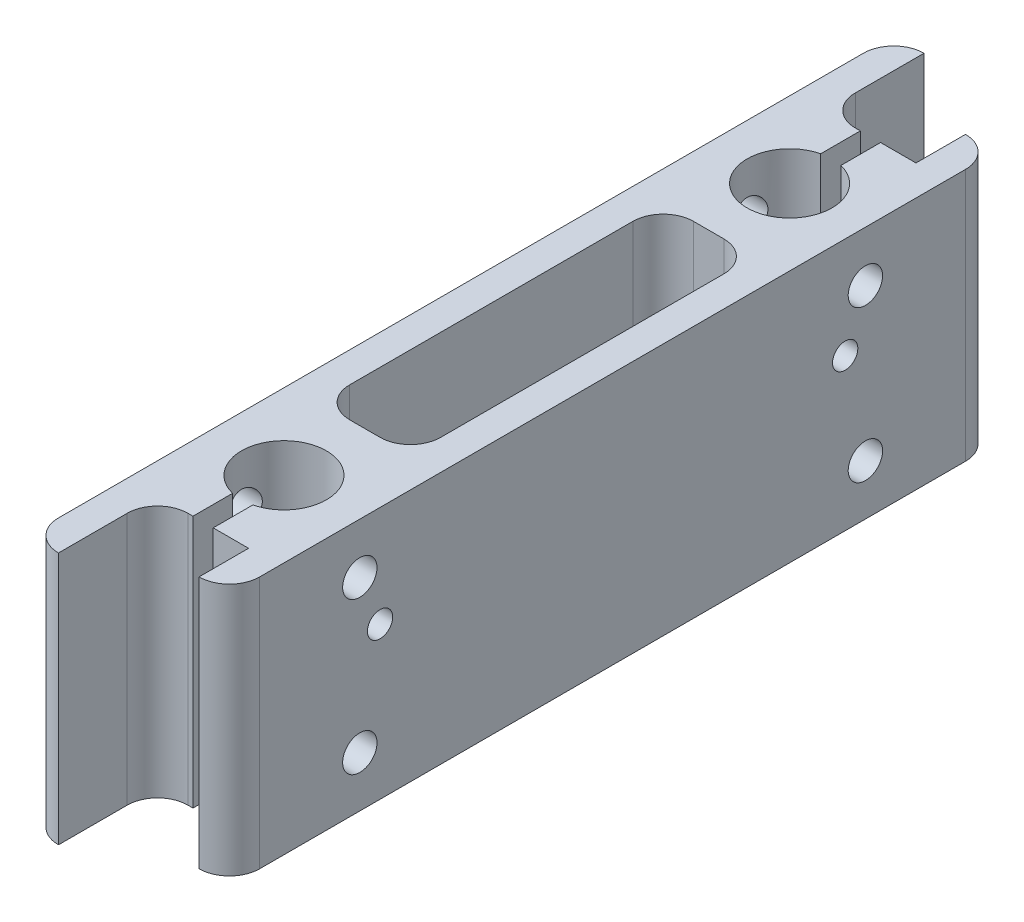
SolidWorks part; units mm, degrees
material "POM 乙缩醛共聚物"
ref_plane "前视基准面" through (0, 0, 0) normal (0, 0, 1) x (1, 0, 0)
ref_plane "上视基准面" through (0, 0, 0) normal (0, 1, 0) x (1, 0, 0)
ref_plane "右视基准面" through (0, 0, 0) normal (1, 0, 0) x (0, 0, -1)
sketch "草图2" plane through (0, 0, 0) normal (0, 1, 0) x (1, 0, 0)
  line L0 (-10.5, 44.6) -> (-10.5, 34.8)
  line L5 (-14.6, 25.2) -> (12.8735, -22.22) construction
  line L6 (4.2, -25.2) -> (-4.2, 25.2) construction
  line L7 (-13.5, 44.6) -> (-10.5, 44.6)
  line L8 (-13.5, 44.6) -> (-13.5, -41)
  line L9 (-13.5, -41) -> (-10.5, -41)
  line L10 (1.5, 39.7) -> (1.5, -36.1)
  line L11 (-13.5, 44.6) -> (10.9271, -36.1) construction
  line L12 (-13.5, -41) -> (13.072, 39.7) construction
  line L13 (-10.5, 34.8) -> (-1.5, 34.8)
  line L14 (-1.5, 34.8) -> (-1.5, 39.7)
  line L15 (-10.5, -41) -> (-10.5, -31.2)
  line L16 (-10.5, -31.2) -> (-1.5, -31.2)
  line L17 (-1.5, -31.2) -> (-1.5, -36.1)
  line L18 (-1.5, 39.7) -> (1.5, 39.7)
  line L19 (-1.5, -36.1) -> (1.5, -36.1)
  circle A0 centre (-6, -23.2) radius 4.2
  circle A1 centre (-6, 26.8) radius 4.2
  point P0 (0, 0)
  point P6 (0, 0)
  dimension "D14" = 8.4
  dimension "D15" = 8.4
  dimension "D4" = 7.5
  dimension "D16" = 8
  dimension "D18" = 8
  dimension "D2" = 50
  dimension "D8" = 7.5
  dimension "D1" = 10.4
  dimension "D3" = 85.6
  dimension "D5" = 9
  dimension "D6" = 3
  dimension "D7" = 3
  dimension "D9" = 3
  dimension "D10" = 4.9
  dimension "D11" = 9.8
  dimension "D12" = 4.9
  dimension "D13" = 9.8
extrude "凸台-拉伸1" add sketch "草图2" along normal blind 25
fillet "圆角1" radius 3 6 edges at (1.5, 12.5, 36.1) (1.5, 12.5, -39.7) (-10.5, 12.5, -34.8) (-10.5, 12.5, 31.2) (-13.5, 12.5, -44.6) (-13.5, 12.5, 41)
sketch "草图3" plane through (0, 25, 0) normal (0, 1, 0) x (1, 0, 0)
  line L5 (-13.5, 41.6) -> (-13.5, -38) construction
  line L6 (-7.5, 18.8) -> (-4.5, 18.8)
  line L7 (-10.5, 15.8) -> (-10.5, -12.2)
  line L8 (-7.5, -15.2) -> (-4.5, -15.2)
  line L9 (-1.5, 15.8) -> (-1.5, -12.2)
  line L10 (-10.5, 18.8) -> (-1.5, -15.2) construction
  line L11 (-10.5, -15.2) -> (-1.5, 18.8) construction
  line L12 (1.5, -33.1) -> (1.5, 36.7) construction
  circle A5 centre (-6, 26.8) radius 4.2 construction
  circle A6 centre (-6, -23.2) radius 4.2 construction
  arc A7 (-10.5, -12.2) -> (-7.5, -15.2) centre (-7.5, -12.2) ccw
  arc A8 (-4.5, -15.2) -> (-1.5, -12.2) centre (-4.5, -12.2) ccw
  arc A9 (-4.5, 18.8) -> (-1.5, 15.8) centre (-4.5, 15.8) cw
  arc A10 (-7.5, 18.8) -> (-10.5, 15.8) centre (-7.5, 15.8) ccw
  point P4 (-6, 1.8)
  dimension "D3" = 8
  dimension "D5" = 3
  dimension "D1" = 3
  dimension "D2" = 3
  dimension "D4" = 8
extrude "切除-拉伸1" cut sketch "草图3" against normal blind 25
sketch "草图4" plane through (0, 25, 0) normal (0, 1, 0) x (1, 0, 0)
  line L1 (-5, -36.7224) -> (-7, -36.7224)
  line L2 (-5, -36.7224) -> (-5, -26.95)
  line L3 (-5, -26.95) -> (-7, -26.95)
  line L4 (-7, -36.7224) -> (-7, -26.95)
  line L5 (-5, -36.7224) -> (-7, -26.95) construction
  line L6 (-5, -26.95) -> (-7, -36.7224) construction
  line L7 (-5, 37.1632) -> (-7, 37.1632)
  line L8 (-5, 37.1632) -> (-5, 27.1332)
  line L9 (-5, 27.1332) -> (-7, 27.1332)
  line L10 (-7, 37.1632) -> (-7, 27.1332)
  line L11 (-5, 37.1632) -> (-7, 27.1332) construction
  line L12 (-5, 27.1332) -> (-7, 37.1632) construction
  circle A0 centre (-6, 26.8) radius 4.2 construction
  circle A1 centre (-6, -23.2) radius 4.2 construction
  point P4 (-6, -31.8362)
  point P9 (-6, 32.1482)
  dimension "D1" = 2
  dimension "D2" = 1
  dimension "D3" = 2
  dimension "D4" = 1
extrude "切除-拉伸2" cut sketch "草图4" against normal blind 25
sketch "草图5" plane through (1.5, 0, 0) normal (1, 0, 0) x (0, 0, -1)
  line L0 (-33.1, 25) -> (36.7, 25) construction
  line L2 (-31.2, 25) -> (-31.2, 0) construction
  line L3 (34.8, 25) -> (34.8, 0) construction
  circle A0 centre (-21.2, 15) radius 1.25
  circle A1 centre (24.8, 15) radius 1.25
  dimension "D1" = 10
  dimension "D2" = 10
  dimension "D3" = 2.5
  dimension "D4" = 2.5
  dimension "D5" = 10
  dimension "D6" = 10
extrude "切除-拉伸3" cut sketch "草图5" against normal blind 35
sketch "草图6" plane through (1.5, 0, 0) normal (1, 0, 0) x (0, 0, -1)
  line L0 (-33.1, 0) -> (36.7, 0) construction
  line L1 (15.8, 0) -> (15.8, 25) construction
  line L2 (-12.2, 0) -> (-12.2, 25) construction
  circle A0 centre (26.8, 5) radius 1.7
  circle A1 centre (26.8, 20) radius 1.7
  circle A2 centre (-23.2, 5) radius 1.7
  circle A3 centre (-23.2, 20) radius 1.7
  dimension "D2" = 11
  dimension "D3" = 3.4
  dimension "D4" = 3.4
  dimension "D5" = 3.4
  dimension "D6" = 3.4
  dimension "D7" = 11
  dimension "D8" = 11
  dimension "D9" = 5
  dimension "D10" = 15
  dimension "D11" = 5
  dimension "D12" = 15
  dimension "D13" = 11
extrude "切除-拉伸4" cut sketch "草图6" against normal blind 32
